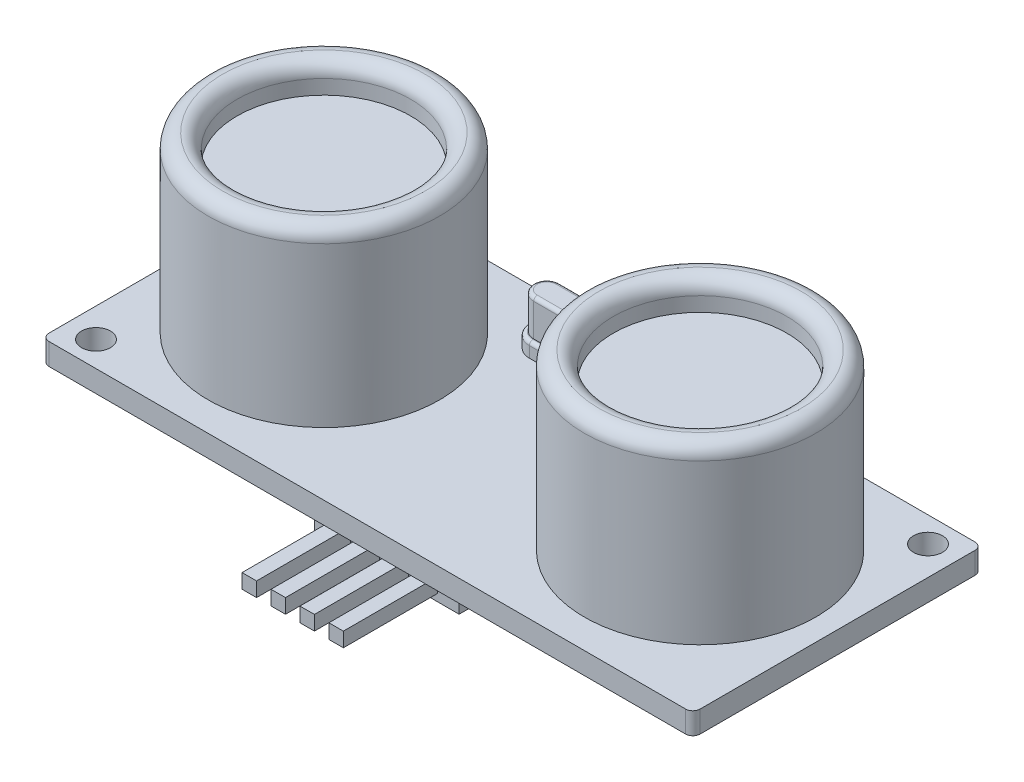
SolidWorks part; units mm, degrees
ref_plane "Front Plane" through (0, 0, 0) normal (0, 0, 1) x (1, 0, 0)
ref_plane "Top Plane" through (0, 0, 0) normal (0, 1, 0) x (1, 0, 0)
ref_plane "Right Plane" through (0, 0, 0) normal (1, 0, 0) x (0, 0, -1)
sketch "Sketch1" plane through (0, 0, 0) normal (0, 1, 0) x (1, 0, 0)
  line L1 (-22.5, -10) -> (22.5, -10)
  line L2 (-22.5, -10) -> (-22.5, 10)
  line L3 (-22.5, 10) -> (22.5, 10)
  line L4 (22.5, -10) -> (22.5, 10)
  line L5 (-22.5, -10) -> (22.5, 10) construction
  line L6 (-22.5, 10) -> (22.5, -10) construction
  point P0 (0, 0)
  dimension "D1" = 20
  dimension "D2" = 45
extrude "Boss-Extrude1" add sketch "Sketch1" along normal blind 1.5
sketch "Sketch2" plane through (0, 1.5, 0) normal (0, 1, 0) x (1, 0, 0)
  line L0 (-22.5, 10) -> (-22.5, -10) construction
  circle A0 centre (-13, 0) radius 8
  circle A1 centre (13, 0) radius 8
  point P4 (-22.5, 0)
  dimension "D1" = 26
  dimension "D2" = 9.5
extrude "Boss-Extrude3" add sketch "Sketch2" along normal blind 12 contours A0 | A1
sketch "Sketch3" plane through (0, 1.5, 0) normal (0, 1, 0) x (1, 0, 0)
  line L0 (-22.5, -10) -> (22.5, -10) construction
  line L1 (-22.5, 10) -> (-22.5, -10) construction
  line L2 (22.5, -10) -> (22.5, 10) construction
  line L4 (22.5, 10) -> (-22.5, 10) construction
  circle A0 centre (-20.5, -8.25) radius 1
  circle A1 centre (20.5, 8.25) radius 1
  dimension "D1" = 1.75
  dimension "D2" = 2
  dimension "D3" = 2
  dimension "D4" = 1.75
extrude "Cut-Extrude1" cut sketch "Sketch3" against normal blind 3 contours A0 | A1
sketch "Sketch4" plane through (0, 13.5, 0) normal (0, 1, 0) x (1, 0, 0)
  circle A0 centre (-13, 0) radius 6
sketch "Sketch5" plane through (0, 13.5, 0) normal (0, 1, 0) x (1, 0, 0)
  circle A0 centre (13, 0) radius 6
extrude "Cut-Extrude2" cut sketch "Sketch4" against normal blind 2 contours A0
extrude "Cut-Extrude3" cut sketch "Sketch5" against normal blind 2 contours A0
fillet "Fillet1" radius 1 4 edges at (13, 13.5, 8) (13, 13.5, 6) (-13, 13.5, 8) (-13, 13.5, 6)
fillet "Fillet2" radius 0.5 4 edges at (-22.5, 0.75, 10) (-22.5, 0.75, -10) (22.5, 0.75, -10) (22.5, 0.75, 10)
sketch "Sketch6" plane through (0, 1.5, 0) normal (0, 1, 0) x (1, 0, 0)
  line L0 (-4.401, 6.8) -> (4.399, 6.8) construction
  line L1 (-4.401, 8) -> (4.399, 8)
  line L2 (-4.401, 5.6) -> (4.399, 5.6)
  arc A0 (-4.401, 8) -> (-4.401, 5.6) centre (-4.401, 6.8) ccw
  arc A1 (4.399, 5.6) -> (4.399, 8) centre (4.399, 6.8) ccw
  point P2 (-0.001, 6.8)
extrude "Boss-Extrude5" add sketch "Sketch6" along normal blind 1
sketch "Sketch7" plane through (0, 2.5, 0) normal (0, 1, 0) x (1, 0, 0)
  line L0 (-4.401, 6.8) -> (4.399, 6.8) construction
  line L1 (-4.401, 7.7) -> (4.399, 7.7)
  line L2 (-4.401, 5.9) -> (4.399, 5.9)
  arc A0 (-4.401, 7.7) -> (-4.401, 5.9) centre (-4.401, 6.8) ccw
  arc A1 (4.399, 5.9) -> (4.399, 7.7) centre (4.399, 6.8) ccw
  point P4 (-0.001, 6.8)
extrude "Boss-Extrude6" add sketch "Sketch7" along normal blind 2.5
fillet "Fillet3" radius 0.25 8 edges at (-5.601, 2.5, -6.8) (-0.001, 2.5, -8) (5.599, 2.5, -6.8) (-5.301, 5, -6.8) (-0.001, 5, -7.7) (5.299, 5, -6.8) (-0.001, 2.5, -5.6) (-0.001, 5, -5.9)
sketch "Sketch8" plane through (0, 0, 0) normal (0, -1, 0) x (1, 0, 0)
  line L1 (5, 8.6549) -> (-5, 8.6549)
  line L2 (5, 8.6549) -> (5, 6.6549)
  line L3 (5, 6.6549) -> (-5, 6.6549)
  line L4 (-5, 8.6549) -> (-5, 6.6549)
  line L5 (5, 8.6549) -> (-5, 6.6549) construction
  line L6 (5, 6.6549) -> (-5, 8.6549) construction
  point P0 (0, 7.6549)
  dimension "D1" = 2
  dimension "D2" = 10
extrude "Boss-Extrude7" add sketch "Sketch8" along normal blind 2
sketch "Sketch9" plane through (0, 0, 8.6549) normal (0, 0, 1) x (1, 0, 0)
  line L0 (-5, -2) -> (-5, 0) construction
  line L1 (-3.5, -1.5048) -> (-2.5, -1.5048)
  line L2 (-3.5, -1.5048) -> (-3.5, -0.5048)
  line L3 (-3.5, -0.5048) -> (-2.5, -0.5048)
  line L4 (-2.5, -1.5048) -> (-2.5, -0.5048)
  line L5 (-3.5, -1.5048) -> (-2.5, -0.5048) construction
  line L6 (-3.5, -0.5048) -> (-2.5, -1.5048) construction
  line L7 (-1.5, -1.5038) -> (-0.5, -1.5038)
  line L8 (-1.5, -1.5038) -> (-1.5, -0.5038)
  line L9 (-1.5, -0.5038) -> (-0.5, -0.5038)
  line L10 (-0.5, -1.5038) -> (-0.5, -0.5038)
  line L11 (-1.5, -1.5038) -> (-0.5, -0.5038) construction
  line L12 (-1.5, -0.5038) -> (-0.5, -1.5038) construction
  line L13 (0.5, -1.5095) -> (1.5, -1.5095)
  line L14 (0.5, -1.5095) -> (0.5, -0.5095)
  line L15 (0.5, -0.5095) -> (1.5, -0.5095)
  line L16 (1.5, -1.5095) -> (1.5, -0.5095)
  line L17 (0.5, -1.5095) -> (1.5, -0.5095) construction
  line L18 (0.5, -0.5095) -> (1.5, -1.5095) construction
  line L19 (2.5, -1.5095) -> (3.5, -1.5095)
  line L20 (2.5, -1.5095) -> (2.5, -0.5095)
  line L21 (2.5, -0.5095) -> (3.5, -0.5095)
  line L22 (3.5, -1.5095) -> (3.5, -0.5095)
  line L23 (2.5, -1.5095) -> (3.5, -0.5095) construction
  line L24 (2.5, -0.5095) -> (3.5, -1.5095) construction
  point P0 (-3, -1.0048)
  point P5 (-2.5681, -1.1609)
  point P6 (-1, -1.0038)
  point P11 (1, -1.0095)
  point P16 (3, -1.0095)
  dimension "D1" = 1
  dimension "D2" = 1
  dimension "D3" = 1
  dimension "D4" = 1
  dimension "D5" = 1
  dimension "D6" = 1
  dimension "D7" = 1
  dimension "D8" = 1
  dimension "D9" = 1
  dimension "D10" = 1
  dimension "D11" = 1
  dimension "D12" = 1.5
extrude "Boss-Extrude9" add sketch "Sketch9" along normal blind 6.5 contours L13 L16 L15 L14 | L7 L10 L9 L8 | L1 L4 L3 L2 | L19 L22 L21 L20
